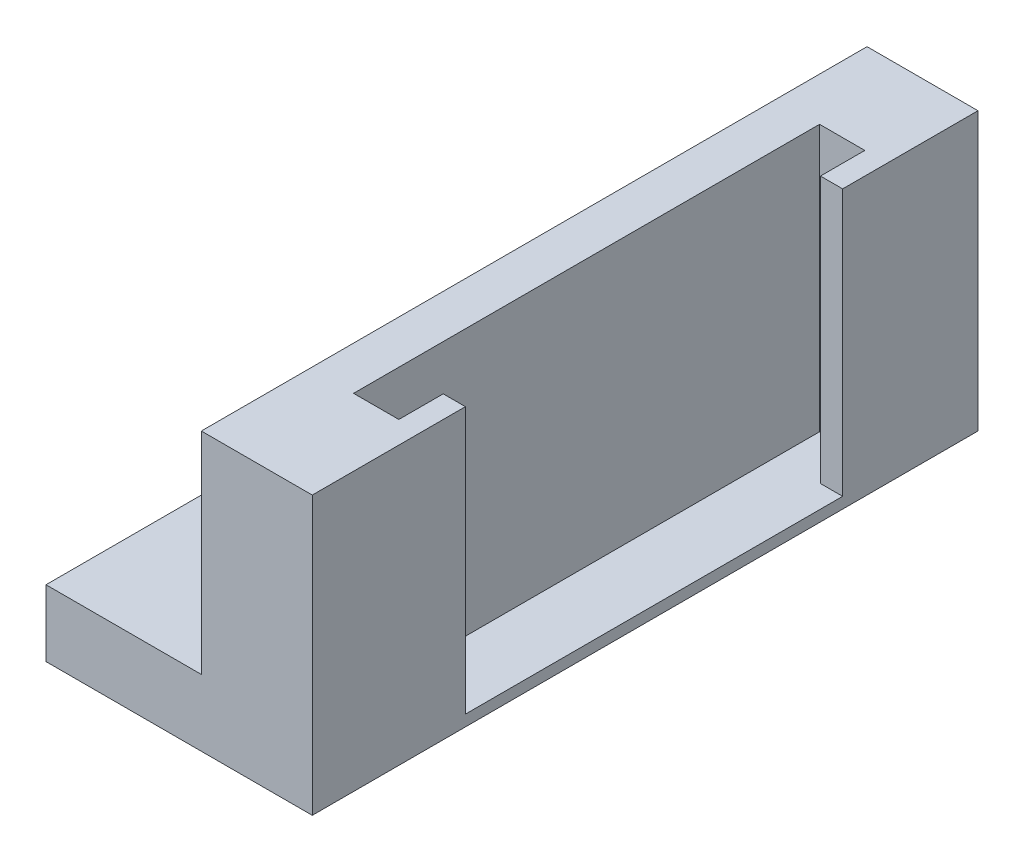
SolidWorks part; units mm, degrees
ref_plane "Alzado" through (0, 0, 0) normal (0, 0, 1) x (1, 0, 0)
ref_plane "Planta" through (0, 0, 0) normal (0, 1, 0) x (1, 0, 0)
ref_plane "Vista lateral" through (0, 0, 0) normal (1, 0, 0) x (0, 0, -1)
sketch "Croquis1" plane through (0, 0, 0) normal (0, 0, 1) x (1, 0, 0)
  line L3 (12, 0) -> (12, 12.5)
  line L4 (12, 12.5) -> (7, 12.5)
  line L5 (7, 12.5) -> (7, 3)
  line L6 (7, 3) -> (0, 3)
  line L7 (0, 3) -> (0, 0)
  line L8 (0, 0) -> (12, 0)
  dimension "D1" = 3
  dimension "D2" = 7
  dimension "D3" = 9.5
  dimension "D5" = 5
extrude "Saliente-Extruir1" add sketch "Croquis1" along normal blind 30
sketch "Croquis2" plane through (0, 12.5, 0) normal (0, 1, 0) x (1, 0, 0)
  line L0 (12, -15) -> (12, -23.1)
  line L1 (12, -30) -> (12, 0) construction
  line L2 (12, -6.1) -> (11, -6.1)
  line L3 (12, -23.1) -> (11, -23.1)
  line L4 (11, -23.1) -> (11, -25.1)
  line L5 (11, -25.1) -> (8.96, -25.1)
  line L6 (8.96, -25.1) -> (8.96, -4.1)
  line L8 (12, -30) -> (7, -30) construction
  line L9 (6.96, -15.4) -> (7.948, -15.4) construction
  line L10 (11, -4.1) -> (8.96, -4.1)
  line L11 (11, -6.1) -> (11, -4.1)
  line L12 (12, -23.1) -> (12, -6.1)
  line L13 (12, -6.1) -> (12, -15)
  line L15 (8.96, -4.1) -> (8.96, 0) construction
  line L16 (12, 0) -> (7, 0) construction
  line M11 (12, -30) -> (12, 0)
  dimension "D1" = 2.04
  dimension "D2" = 1
  dimension "D3" = 2
  dimension "D4" = 4.9
  dimension "D5" = 21
  dimension "D6" = 1
extrude "Cortar-Extruir1" cut sketch "Croquis2" against normal blind 12 contours L2 L11 L10 L6 L5 L4 L3 M11 region at (10.4118, 12.5, 14.6)
sketch "Croquis3" plane through (0, 3, 0) normal (0, 1, 0) x (1, 0, 0)
  line L0 (3.5, 0) -> (3.5, -6) construction
  line L1 (3.5, -6) -> (7, -6) construction
  line L2 (7, -30) -> (7, 0) construction
  line L5 (0, -30) -> (0, 0) construction
  line L6 (0, -15) -> (2.5, -15) construction
  circle A0 centre (3.5, -6) radius 1.65
  circle A1 centre (3.5, -24) radius 1.65
  dimension "D1" = 3.3
  dimension "D2" = 6
  dimension "D3" = 3.5
extrude "Cortar-Extruir2" cut sketch "Croquis3" against normal up to next
